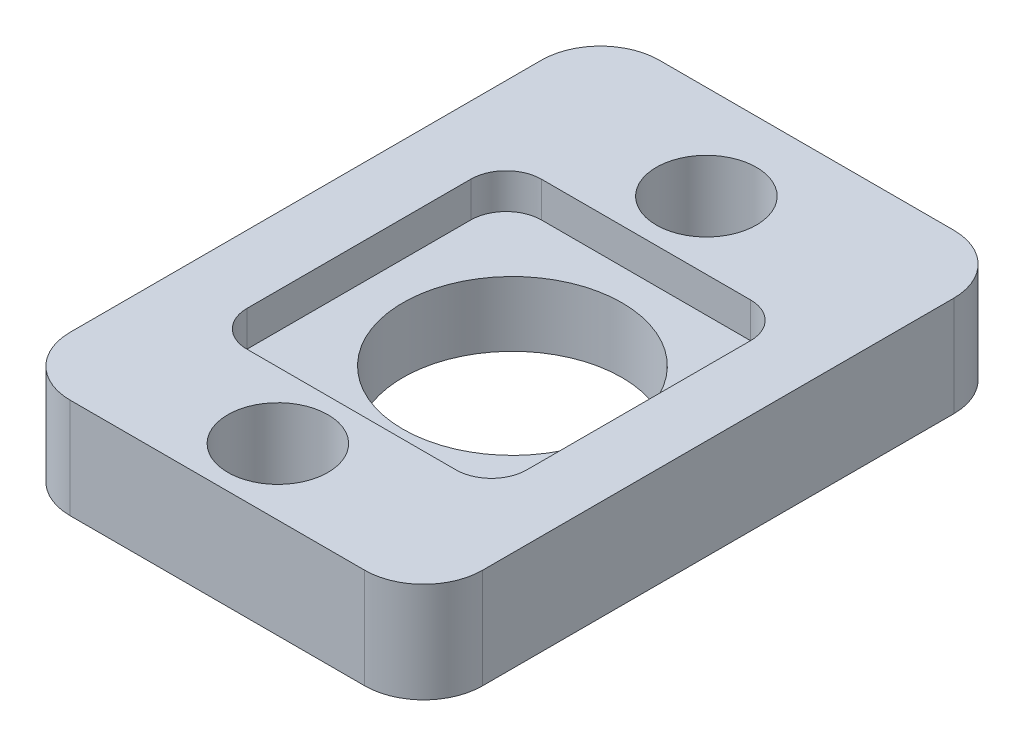
SolidWorks part; units mm, degrees
ref_plane "Front Plane" through (0, 0, 0) normal (0, 0, 1) x (1, 0, 0)
ref_plane "Top Plane" through (0, 0, 0) normal (0, 1, 0) x (1, 0, 0)
ref_plane "Right Plane" through (0, 0, 0) normal (1, 0, 0) x (0, 0, -1)
sketch "Sketch1" plane through (0, 0, 0) normal (0, 1, 0) x (1, 0, 0)
  line L1 (2, 0) -> (12, 0)
  line L2 (0, -2) -> (0, -18)
  line L3 (2, -20) -> (12, -20)
  line L4 (14, -2) -> (14, -18)
  arc A0 (0, -18) -> (2, -20) centre (2, -18) ccw
  arc A1 (12, -20) -> (14, -18) centre (12, -18) ccw
  arc A2 (12, 0) -> (14, -2) centre (12, -2) cw
  arc A3 (2, 0) -> (0, -2) centre (2, -2) ccw
  point P7 (0, -20)
  point P12 (14, 0)
  point P15 (0, 0)
  dimension "D3" = 2
  dimension "D1" = 14
  dimension "D2" = 20
extrude "Boss-Extrude1" add sketch "Sketch1" along normal blind 3.4
sketch "Sketch2" plane through (0, 3.4, 0) normal (0, 1, 0) x (1, 0, 0)
  line L0 (12, 0) -> (2, 0) construction
  line L1 (3.5, -5.5) -> (10.6, -5.5)
  line L2 (2.3, -6.7) -> (2.3, -14.3)
  line L3 (3.5, -15.5) -> (10.6, -15.5)
  line L4 (11.8, -6.7) -> (11.8, -14.3)
  line L5 (14, -18) -> (14, -2) construction
  arc A0 (2.3, -14.3) -> (3.5, -15.5) centre (3.5, -14.3) ccw
  arc A1 (10.6, -15.5) -> (11.8, -14.3) centre (10.6, -14.3) ccw
  arc A2 (10.6, -5.5) -> (11.8, -6.7) centre (10.6, -6.7) cw
  arc A3 (3.5, -5.5) -> (2.3, -6.7) centre (3.5, -6.7) ccw
  point P4 (7.05, -5.5)
  point P9 (2.3, -15.5)
  point P14 (11.8, -5.5)
  point P17 (2.3, -5.5)
  dimension "D4" = 1.2
  dimension "D1" = 9.5
  dimension "D2" = 10
  dimension "D3" = 5.5
  dimension "D5" = 2.2
extrude "Cut-Extrude1" cut sketch "Sketch2" against normal blind 1.2
sketch "Sketch3" plane through (0, 2.2, 0) normal (0, 1, 0) x (1, 0, 0)
  line L0 (11.8, -14.3) -> (11.8, -6.7) construction
  circle A0 centre (7.3, -10.2854) radius 3.72
  point P2 (0, 0)
  point P3 (7.3, -12.5598)
  point P4 (7.3, -15)
  point P5 (7.3, -11.1699)
  point P6 (0, 0)
  point P7 (7.3, -10.2854)
  dimension "D1" = 7.44
  dimension "D2" = 4.5
extrude "Cut-Extrude2" cut sketch "Sketch3" against normal through all
sketch "Sketch4" plane through (0, 3.4, 0) normal (0, 1, 0) x (1, 0, 0)
  line L0 (0, -10.4749) -> (25.4035, -10.4749) construction
  line L1 (0, -2) -> (0, -18) construction
  line L2 (12, 0) -> (2, 0) construction
  circle A0 centre (6.8, -3.2) radius 1.7
  circle A2 centre (6.8, -17.7498) radius 1.7
  point P10 (0, -12.5)
  dimension "D1" = 3.2
  dimension "D2" = 6.8
extrude "Cut-Extrude3" cut sketch "Sketch4" against normal through all
